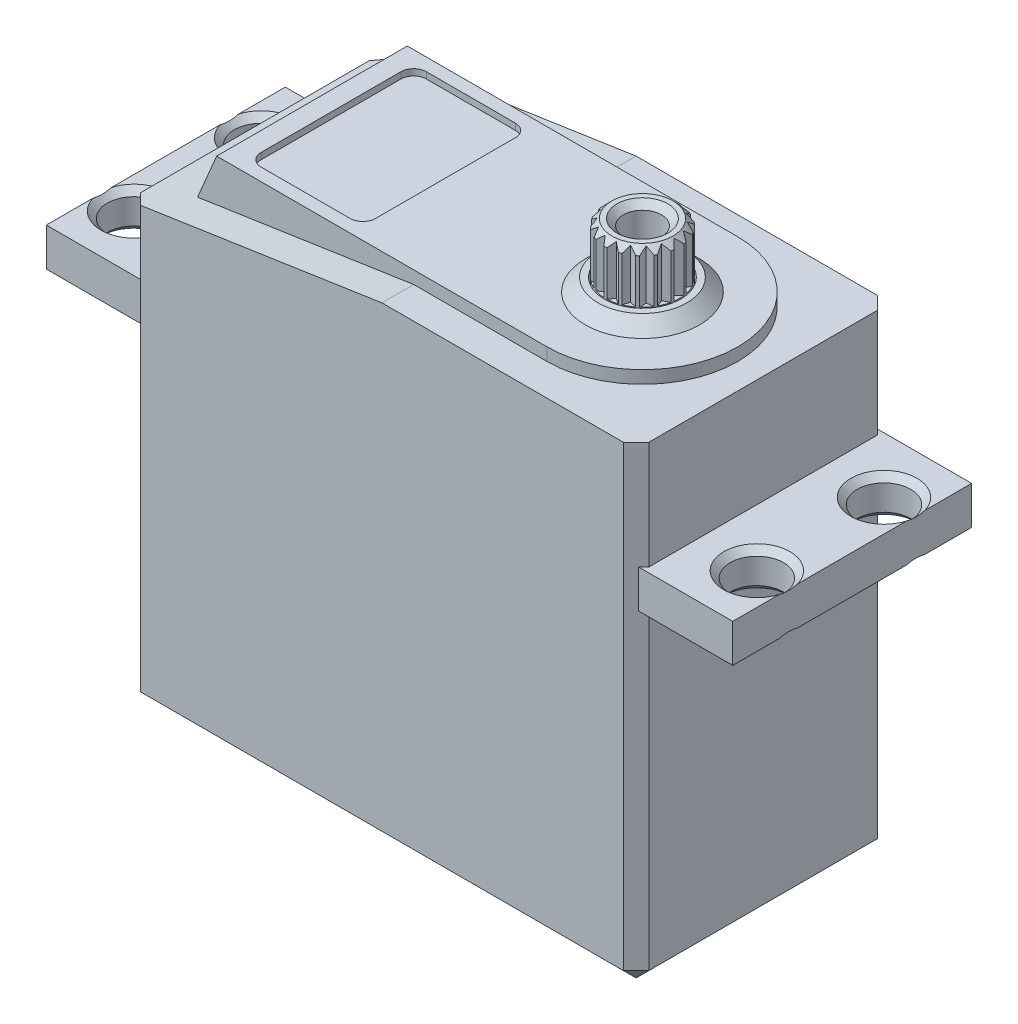
SolidWorks part; units mm, degrees
ref_plane "前视基准面" through (0, 0, 0) normal (0, 0, 1) x (1, 0, 0)
ref_plane "上视基准面" through (0, 0, 0) normal (0, 1, 0) x (1, 0, 0)
ref_plane "右视基准面" through (0, 0, 0) normal (1, 0, 0) x (0, 0, -1)
sketch "草图1" plane through (0, 0, 0) normal (0, 1, 0) x (1, 0, 0)
  line L0 (0, 0) -> (9.5, 0) construction
  line L1 (9.5, -10) -> (9.5, 10)
  line L2 (9.5, 10) -> (-30.5, 10)
  line L3 (-30.5, 10) -> (-30.5, -10)
  line L4 (-30.5, 0) -> (0, 0) construction
  line L5 (9.5, -10) -> (-30.5, -10)
  dimension "D1" = 9.5
  dimension "D2" = 30.5
  dimension "D3" = 10
extrude "凸台-拉伸1" add sketch "草图1" against normal blind 38
sketch "草图2" plane through (0, 0, 0) normal (0, 1, 0) x (1, 0, 0)
  circle A0 centre (0, 0) radius 2.9
  dimension "D1" = 5.8
extrude "凸台-拉伸2" add sketch "草图2" along normal blind 5
sketch "草图3" plane through (0, 0, 0) normal (0, 1, 0) x (1, 0, 0)
  line L0 (9.5, -10) -> (9.5, 10) construction
  line L1 (2.5, -9.4) -> (16.5, -9.4)
  line L2 (2.5, -9.4) -> (2.5, 9.4)
  line L3 (2.5, 9.4) -> (16.5, 9.4)
  line L4 (16.5, -9.4) -> (16.5, 9.4)
  line L5 (2.5, -9.4) -> (16.5, 9.4) construction
  line L6 (2.5, 9.4) -> (16.5, -9.4) construction
  line L7 (16.5, 0) -> (2.5, 0) construction
  line L8 (-10.5, 10) -> (-10.5, -10) construction
  line L9 (9.5, 10) -> (-30.5, 10) construction
  line L10 (-30.5, -10) -> (9.5, -10) construction
  line L11 (-37.5, 0) -> (-23.5, 0) construction
  line L12 (-23.5, 9.4) -> (-37.5, -9.4) construction
  line L13 (-23.5, -9.4) -> (-37.5, 9.4) construction
  line L14 (-37.5, -9.4) -> (-37.5, 9.4)
  line L15 (-23.5, 9.4) -> (-37.5, 9.4)
  line L16 (-23.5, -9.4) -> (-23.5, 9.4)
  line L17 (-23.5, -9.4) -> (-37.5, -9.4)
  circle A0 centre (14, 5) radius 2.1
  circle A1 centre (-35, 5) radius 2.1
  circle A2 centre (-35, -5) radius 2.1
  circle A3 centre (14, -5) radius 2.1
  point P0 (9.5, 0)
  point P25 (-30.5, 0)
  dimension "D1" = 4.5
  dimension "D2" = 5
  dimension "D3" = 4.2
  dimension "D4" = 18.8
  dimension "D5" = 54
extrude "凸台-拉伸3" add sketch "草图3" against normal blind 3 from offset 9.5 offset against normal yes
chamfer "倒角1" distance 0.5 angle 45 8 edges at (-35, -9.5, -7.1) (-35, -12.5, -7.1) (-35, -9.5, 7.1) (-35, -12.5, 7.1) (14, -9.5, 2.9) (14, -12.5, 2.9) (14, -9.5, -2.9) (14, -12.5, -2.9)
chamfer "倒角2" distance 1 angle 45 12 edges at (-30.5, -38, 0) (9.5, -38, 0) (9.5, -19, 10) (-10.5, -38, 10) (-30.5, -19, 10) (9.5, 0, 0) (-10.5, 0, 10) (-30.5, 0, 0) (-30.5, -19, -10) (-10.5, -38, -10) (9.5, -19, -10) (-10.5, 0, -10)
sketch "草图4" plane through (0, 5, 0) normal (0, 1, 0) x (1, 0, 0)
  line L0 (0, 0) -> (2.7, 0) construction
  line L1 (2.8716, 0.4048) -> (2.5, 0)
  line L2 (2.8716, 0.4048) -> (0, 0) construction
  line L3 (0, 0) -> (2.8559, 0.5036)
  line L4 (0, 0) -> (2.8559, -0.5036)
  line L5 (2.8716, -0.4048) -> (2.5, 0)
  circle A1 centre (0, 0) radius 2.9 construction
  arc A2 (2.8716, 0.4048) -> (2.8716, -0.4048) centre (0, 0) cw
  circle M6 centre (0, 0) radius 2.9
  dimension "D4" = 2.9
  dimension "D1" = 0.2
  dimension "D2" = 20
  dimension "D3" = 0.1
  dimension "D5" = 2.5
extrude "切除-拉伸1" cut sketch "草图4" against normal blind 4 and the other way through all contours L5 L1 M6
pattern_circular "阵列(圆周)1" count 18 over 360 about axis through (-0.0174, 0, 0) along (0, 1, 0) of "切除-拉伸1"
sketch "草图5" plane through (0, 5, 0) normal (0, 1, 0) x (1, 0, 0)
  circle A0 centre (0, 0) radius 1.5
  dimension "D1" = 3
extrude "切除-拉伸2" cut sketch "草图5" against normal blind 5
sketch "草图6" plane through (0, 0, 0) normal (0, 1, 0) x (1, 0, 0)
  line L0 (0, 7.5) -> (-27, 7.5)
  line L1 (-27, 7.5) -> (-27, -7.5)
  line L2 (-27, 0) -> (-7.5, 0) construction
  line L3 (0, -7.5) -> (-27, -7.5)
  arc A0 (0, -7.5) -> (0, 7.5) centre (0, 0) ccw
  arc A1 (0, 7.5) -> (-7.5, 0) centre (0, 0) ccw construction
  arc A2 (-7.5, 0) -> (0, -7.5) centre (0, 0) ccw construction
  dimension "D1" = 15
  dimension "D2" = 27
extrude "切除-拉伸4" cut sketch "草图6" against normal blind 1 flip side to cut
sketch "草图7" plane through (0, 0, -7.5) normal (0, 0, -1) x (-1, 0, 0)
  line L0 (10.5, -1) -> (30.5, -4)
  line L1 (29.5, -1) -> (-8.5, -1) construction
  line L2 (30.5, -1) -> (30.5, -9.5) construction
  line L3 (30.5, -4) -> (30.5, -1)
  line L4 (30.5, -1) -> (10.5, -1)
  dimension "D1" = 3
extrude "切除-拉伸5" cut sketch "草图7" along normal blind 11
mirror "镜向1" about plane through (0, 0, 0) normal (0, 0, 1) of "切除-拉伸5"
sketch "草图8" plane through (0, 0, -7.5) normal (0, 0, -1) x (-1, 0, 0)
  line L0 (26, 0) -> (27.5, -3.55)
  line L1 (0, 0) -> (27, 0) construction
  line L2 (29.5, -3.85) -> (10.5, -1) construction
  line L3 (27.5, -3.55) -> (30.5, -4)
  line L4 (30.5, -4) -> (30.5, 0)
  line L5 (30.5, 0) -> (26, 0)
  dimension "D1" = 4.5
  dimension "D2" = 3
extrude "切除-拉伸6" cut sketch "草图8" against normal through all both and the other way through all
sketch "草图9" plane through (0, 0, 0) normal (0, 1, 0) x (1, 0, 0)
  circle A0 centre (0, 0) radius 4.5
  circle A1 centre (0, 0) radius 3
  dimension "D1" = 6
  dimension "D2" = 9
extrude "凸台-拉伸4" add sketch "草图9" along normal blind 1
chamfer "倒角4" distance 1 angle 45 1 edges at (0, 1, 4.5)
chamfer "倒角5" distance 0.5 angle 45 2 edges at (0, 5, 1.5)
sketch "草图10" plane through (0, 0, 0) normal (0, 1, 0) x (1, 0, 0)
  line L0 (0, 0) -> (-20, 0) construction
  line L1 (-24.5, 6.5) -> (-15.5, 6.5)
  line L2 (-24.5, 6.5) -> (-24.5, -6.5)
  line L3 (-24.5, -6.5) -> (-15.5, -6.5)
  line L4 (-15.5, 6.5) -> (-15.5, -6.5)
  line L5 (-24.5, 6.5) -> (-15.5, -6.5) construction
  line L6 (-24.5, -6.5) -> (-15.5, 6.5) construction
  line L7 (-26, 0) -> (-20, 0) construction
  line L8 (-26, -7.5) -> (-26, 7.5) construction
  point P0 (-20, 0)
  dimension "D1" = 13
  dimension "D2" = 9
  dimension "D3" = 20
extrude "切除-拉伸7" cut sketch "草图10" against normal blind 0.5
fillet "圆角1" radius 1 4 edges at (-24.5, -0.25, 6.5) (-24.5, -0.25, -6.5) (-15.5, -0.25, -6.5) (-15.5, -0.25, 6.5)
